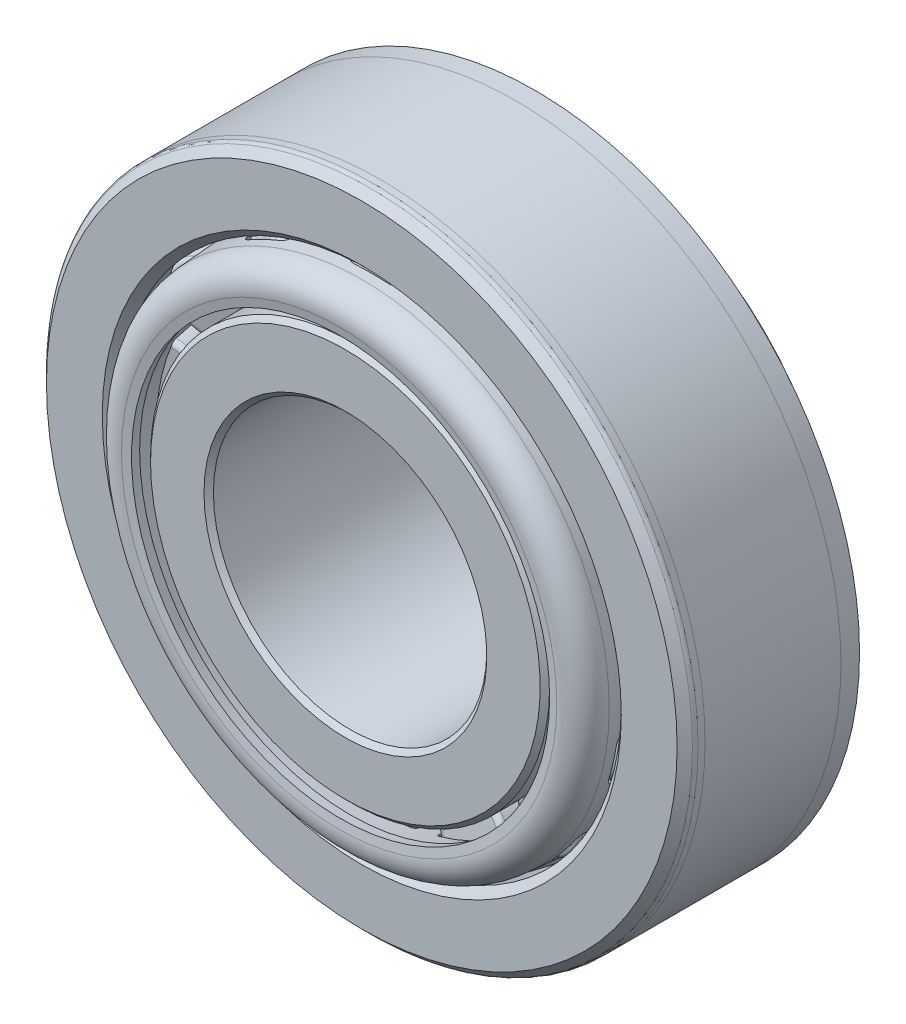
SolidWorks part; units mm, degrees
ref_plane "Front Plane" through (0, 0, 0) normal (0, 0, 1) x (1, 0, 0)
ref_plane "Top Plane" through (0, 0, 0) normal (0, 1, 0) x (1, 0, 0)
ref_plane "Right Plane" through (0, 0, 0) normal (1, 0, 0) x (0, 0, -1)
sketch "Sketch1" plane through (0, 0, 0) normal (1, 0, 0) x (0, 0, -1)
  line L0 (-6.0325, 22.6219) -> (-6.0325, 17.435)
  line L1 (-6.0325, 17.435) -> (6.0325, 19.845)
  line L2 (6.0325, 19.845) -> (6.0325, 22.6219)
  line L3 (6.0325, 22.6219) -> (-6.0325, 22.6219)
  line L4 (0, 0) -> (10110.1541, 0) construction
  line L5 (0.1444, 18.6688) -> (3.8735, 0) construction
  line L6 (9.4615, 15.62) -> (9.4615, 9.525)
  line L7 (9.4615, 9.525) -> (-7.1755, 9.525)
  line L8 (-7.1755, 9.525) -> (-7.1755, 13.905)
  line L9 (-7.1755, 13.905) -> (-4.7866, 13.905)
  line L10 (9.4615, 15.62) -> (6.1102, 15.62)
  line L12 (9.4615, 22.6219) -> (-7.6835, 22.6219) construction
  line L14 (-7.6835, 15.5887) -> (9.0914, 18.452)
  line L15 (9.0914, 18.452) -> (9.2075, 17.7718)
  line L16 (9.2075, 17.7718) -> (-6.8872, 15.0246)
  line L17 (-6.8872, 15.0246) -> (-6.8292, 14.6846)
  line L18 (-5.4103, 17.5593) -> (5.4103, 19.7207) construction
  line L19 (-7.6835, 15.5887) -> (-7.5094, 14.5685)
  line L20 (-7.5094, 14.5685) -> (-6.8292, 14.6846)
  line L21 (5.4103, 19.7207) -> (6.3559, 14.1808)
  line L22 (6.3559, 14.1808) -> (-4.569, 12.6306)
  line L23 (-4.569, 12.6306) -> (-5.4103, 17.5593)
  line L25 (-4.9897, 15.0949) -> (5.8831, 16.9508) construction
  line L27 (0, 18.64) -> (0.4467, 16.0229) construction
  line L28 (0.4467, 16.0229) -> (0.8934, 13.4057) construction
  line L29 (-7.6835, 22.6219) -> (-7.6835, 15.5887) construction
  point P7 (0, 22.6219)
  point P44 (5.841, 17.1972)
  dimension "Width" = 12.065
  dimension "Inner Ring Width" = 16.637
  dimension "Effective Center" = 5.588
  dimension "Width A" = 15.494
  dimension "Cone Thick" = 0.69
  dimension "D17" = 0.345
  dimension "Roller S Diameter" = 5
  dimension "Roller L Diameter" = 5.62
  dimension "Roller Length" = 11.03
  dimension "D2" = 0.25
  dimension "Back Cone Dim" = 0.254
  dimension "Diameter B" = 34.87
  dimension "Diameter C" = 27.81
  dimension "Diameter F" = 39.69
  dimension "Diameter E" = 31.24
  dimension "D3" = 17.145
  dimension "ID" = 19.05
  dimension "OD" = 45.2437
  dimension "Cage Width" = 17.145
sketch "Sketch0" plane through (0, 0, 0) normal (0, 0, 1) x (1, 0, 0)
  circle A0 centre (0, 0) radius 9.525
  circle A1 centre (0, 0) radius 22.6219
  dimension "D1" = 45.2438
  dimension "D2" = 19.05
sketch "Sketch2" plane through (0, 0, 0) normal (1, 0, 0) x (0, 0, -1)
  line L0 (-6.0325, 22.6219) -> (-6.0325, 17.435)
  line L1 (-6.0325, 17.435) -> (6.0325, 19.845)
  line L2 (6.0325, 19.845) -> (6.0325, 22.6219)
  line L3 (6.0325, 22.6219) -> (-6.0325, 22.6219)
revolve "Revolve1" add sketch "Sketch2" angle 360 about L4
sketch "Sketch3" plane through (0, 0, 0) normal (1, 0, 0) x (0, 0, -1)
  line L0 (-7.1755, 13.905) -> (-7.1755, 9.525)
  line L1 (-7.1755, 9.525) -> (9.4615, 9.525)
  line L2 (9.4615, 9.525) -> (9.4615, 15.62)
  line L3 (9.4615, 15.62) -> (6.1102, 15.62)
  line L4 (6.1102, 15.62) -> (6.3559, 14.1808)
  line L5 (6.3559, 14.1808) -> (-4.569, 12.6306)
  line L6 (-4.569, 12.6306) -> (-4.7866, 13.905)
  line L7 (-4.7866, 13.905) -> (-7.1755, 13.905)
revolve "Revolve2" add sketch "Sketch3" angle 360 about L4
sketch "Sketch4" plane through (0, 0, 0) normal (1, 0, 0) x (0, 0, -1)
  line L0 (9.2075, 17.7718) -> (9.0914, 18.452)
  line L1 (9.0914, 18.452) -> (-7.9358, 17.0666)
  line L2 (-7.9358, 17.0666) -> (-7.5094, 14.5685)
  line L3 (-7.5094, 14.5685) -> (-6.8292, 14.6846)
  line L4 (-6.8292, 14.6846) -> (-6.8872, 15.0246)
  line L5 (-6.8872, 15.0246) -> (9.2075, 17.7718)
  line L6 (-5.4103, 17.5593) -> (-7.6835, 15.5887) construction
  line L7 (-6.5469, 16.574) -> (-5.4103, 17.5593) construction
  point P14 (-5.9786, 17.0666)
revolve "Revolve3" add sketch "Sketch4" angle 360 about L4
sketch "Sketch6" plane through (0, 0, 0) normal (1, 0, 0) x (0, 0, -1)
  line L0 (6.3559, 14.1808) -> (5.8831, 16.9508)
  line L1 (5.8831, 16.9508) -> (-4.9897, 15.0949)
  line L3 (-4.9897, 15.0949) -> (-4.569, 12.6306)
  line L4 (-4.569, 12.6306) -> (6.3559, 14.1808)
  line L5 (-4.9897, 15.0949) -> (5.8831, 16.9508) construction
  line L6 (-4.569, 12.6306) -> (-5.4103, 17.5593) construction
revolve "Revolve4" add sketch "Sketch6" angle 360 about L25
sketch "Sketch8" plane through (0, 1.4556, -8.5279) normal (0, 0.1683, -0.9857) x (-1, 0, 0)
  line L0 (0, 12.9093) -> (0, 15.7193) construction
  circle A0 centre (0, 15.7193) radius 1.405
  point P3 (0, 14.3143)
extrude "Cut-Extrude1" cut sketch "Sketch8" against normal blind 0.635
fillet "Fillet7" radius 0.9525 1 edges at (0, 18.2289, -5.0207)
chamfer "Chamfer4" distance 0.3512 angle 45 1 edges at (0, 14.1808, -6.3559)
fillet "Fillet8" radius 0.375 1 edges at (0, 12.6306, 4.569)
pattern_circular "CirPattern1" count 14 over 360 about axis through (0, 0, 0) along (0, 0, 1) of "Revolve4"
fillet "Fillet9" radius 1.765 1 edges at (17.0666, 0, 7.9358)
fillet "Fillet10" radius 0.2243 2 edges at (18.452, 0, -9.0914) (17.7718, 0, -9.2075)
sketch "Sketch9" plane through (0, 0, 0) normal (1, 0, 0) x (0, 0, -1)
  line L0 (-4.9897, 15.0949) -> (5.8831, 16.9508)
  line L1 (5.8831, 16.9508) -> (6.3874, 13.9959)
  line L2 (6.3874, 13.9959) -> (-4.5375, 12.4457)
  line L3 (-4.5375, 12.4457) -> (-4.9897, 15.0949)
  line L4 (-4.569, 12.6306) -> (6.3559, 14.1808) construction
  dimension "D1" = 0.1875
revolve "Cut-Revolve2" cut sketch "Sketch9" angle 360 about L0
fillet "Fillet11" radius 0.25 4 edges at (-2.4056, 16.2762, 5.1913) (2.4056, 16.2762, 5.1913) (2.9532, 17.4571, -5.7967) (-2.9532, 17.4571, -5.7967)
pattern_circular "CirPattern2" count 14 over 360 about axis through (0, 0, 0) along (0, 0, 1) of "Cut-Revolve2", "Fillet11"
chamfer "Chamfer1" distance 0.6484 angle 45 2 edges at (22.6219, 0, 6.0325) (17.435, 0, 6.0325)
ref_plane "Plane1" through (0, 0, 4.7358) normal (0, 0, 1) x (1, 0, 0)
ref_plane "Plane2" through (0, 0, -4.7358) normal (0, 0, -1) x (-1, 0, 0)
split line "Split Line1"
split line "Split Line2"
fillet "Fillet6" radius 0.389 1 edges at (-22.6219, 0, 5.3841)
chamfer "Chamfer2" distance 0.3285 angle 45 2 edges at (13.905, 0, 7.1755) (9.525, 0, 7.1755)
chamfer "Chamfer3" distance 0.6095 angle 45 2 edges at (9.525, 0, -9.4615) (15.62, 0, -9.4615)
sketch "Sketch7" plane through (0, 0, 0) normal (1, 0, 0) x (0, 0, -1)
  line L0 (9.4615, 15.62) -> (9.4615, 9.525) construction
  line L1 (-7.1755, 13.905) -> (-4.7866, 13.905) construction
  line L2 (-7.1755, 9.525) -> (-7.1755, 13.905) construction
  line L3 (9.4615, 9.525) -> (-7.1755, 9.525) construction
  line L4 (9.4615, 15.62) -> (6.1102, 15.62) construction
  line L5 (6.3559, 14.1808) -> (-4.569, 12.6306) construction
  line L6 (5.4103, 19.7207) -> (6.3559, 14.1808) construction
  line L7 (-6.0325, 17.435) -> (6.0325, 19.845) construction
  line L8 (-4.569, 12.6306) -> (-5.4103, 17.5593) construction
  line L9 (9.4615, 15.62) -> (9.4615, 9.525)
  line L10 (-7.1755, 13.905) -> (-4.7866, 13.905)
  line L11 (-7.1755, 9.525) -> (-7.1755, 13.905)
  line L12 (9.4615, 9.525) -> (-7.1755, 9.525)
  line L13 (9.4615, 15.62) -> (6.1102, 15.62)
  line L14 (6.3559, 14.1808) -> (-4.569, 12.6306)
  line L15 (5.4103, 19.7207) -> (6.3559, 14.1808)
  line L16 (-5.4103, 17.5593) -> (5.4103, 19.7207)
  line L17 (-4.569, 12.6306) -> (-5.4103, 17.5593)
  line L18 (0, 0) -> (9.4615, 0) construction
  line L21 (-4.569, -12.6306) -> (-5.4103, -17.5593)
  line L22 (-5.4103, -17.5593) -> (5.4103, -19.7207)
  line L23 (5.4103, -19.7207) -> (6.3559, -14.1808)
  line L24 (6.3559, -14.1808) -> (-4.569, -12.6306)
  line L25 (9.4615, -15.62) -> (6.1102, -15.62)
  line L26 (9.4615, -9.525) -> (-7.1755, -9.525)
  line L27 (-7.1755, -9.525) -> (-7.1755, -13.905)
  line L28 (-7.1755, -13.905) -> (-4.7866, -13.905)
  line L29 (9.4615, -15.62) -> (9.4615, -9.525)
equation "\"D17@Sketch1\" = \"Cone Thick@Sketch1\" / 2"
equation "\"D1@Chamfer1\"=(\"OD@Sketch1\"-\"Diameter B@Sketch1\")*0.5*0.125"
equation "\"D1@Plane1\"=(\"OD@Sketch1\"-\"Diameter B@Sketch1\")*0.5*0.25"
equation "\"D1@Plane2\"=(\"OD@Sketch1\"-\"Diameter B@Sketch1\")*0.5*0.25"
equation "\"D1@Fillet6\"=(\"OD@Sketch1\"-\"Diameter B@Sketch1\")*0.5*0.075"
equation "\"D1@Chamfer2\"=(\"Diameter C@Sketch1\"-\"ID@Sketch1\")*0.5*0.075"
equation "\"D1@Chamfer3\"=(\"Diameter E@Sketch1\"-\"ID@Sketch1\")*0.5*0.1"
equation "\"D1@Chamfer4\"=\"Roller L Diameter@Sketch1\"*0.0625"
equation "\"D1@Fillet8\"=\"Roller S Diameter@Sketch1\"*0.075"
equation "\"D1@Fillet9\"=(\"Diameter B@Sketch1\"-\"Diameter C@Sketch1\")*0.5*0.5"
equation "\"D1@Fillet10\"=\"Cone Thick@Sketch1\"*0.325"
equation "\"D1@Sketch9\"=\"Roller S Diameter@Sketch1\"*0.0375"
equation "\"D1@Fillet11\"=\"Roller S Diameter@Sketch1\"*0.05"
equation "\"D1@CirPattern2\"=\"Number of Rollers@CirPattern1\""
